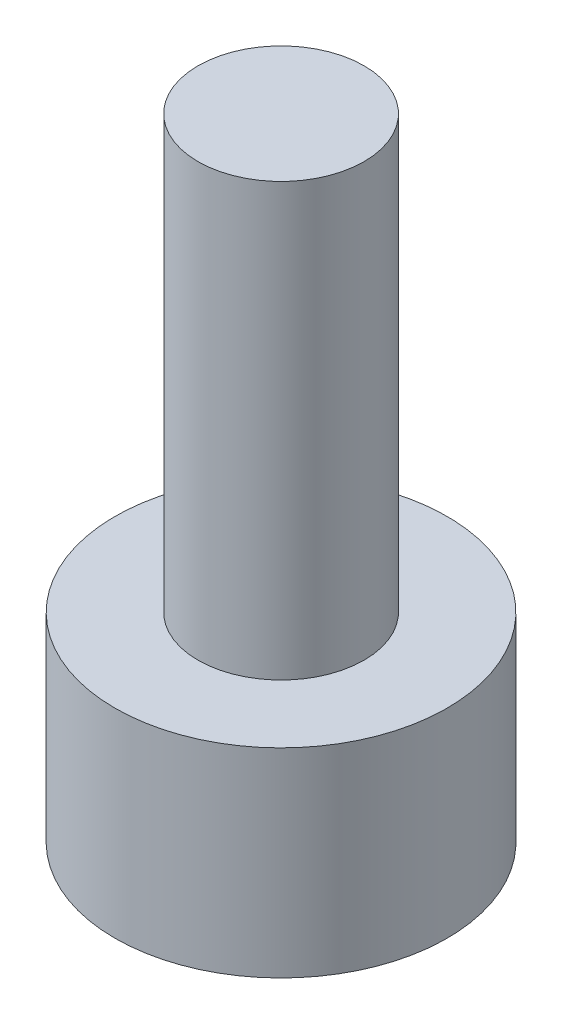
SolidWorks part; units mm, degrees
ref_plane "Front Plane" through (0, 0, 0) normal (0, 0, 1) x (1, 0, 0)
ref_plane "Top Plane" through (0, 0, 0) normal (0, 1, 0) x (1, 0, 0)
ref_plane "Right Plane" through (0, 0, 0) normal (1, 0, 0) x (0, 0, -1)
sketch "Sketch2" plane through (0, 0, 0) normal (0, 1, 0) x (1, 0, 0)
  circle A0 centre (0, 0) radius 5
  circle A1 centre (0, 0) radius 2.5
  dimension "D1" = 10
  dimension "D2" = 5
extrude "Boss-Extrude1" add sketch "Sketch2" along normal blind 6 contours A1 | A0 A1 region at (-4.8586, 0, 0) region at (0, 0, 0)
extrude "Boss-Extrude2" add sketch "Sketch2<3>" along normal blind 13 from surface contours A1 region at (0, 0, 0) starting at face at (0, 6, 5)
sketch "Sketch2<3>" plane through (0, 0, 0) normal (0, 1, 0) x (1, 0, 0) same geometry as "Sketch2"
